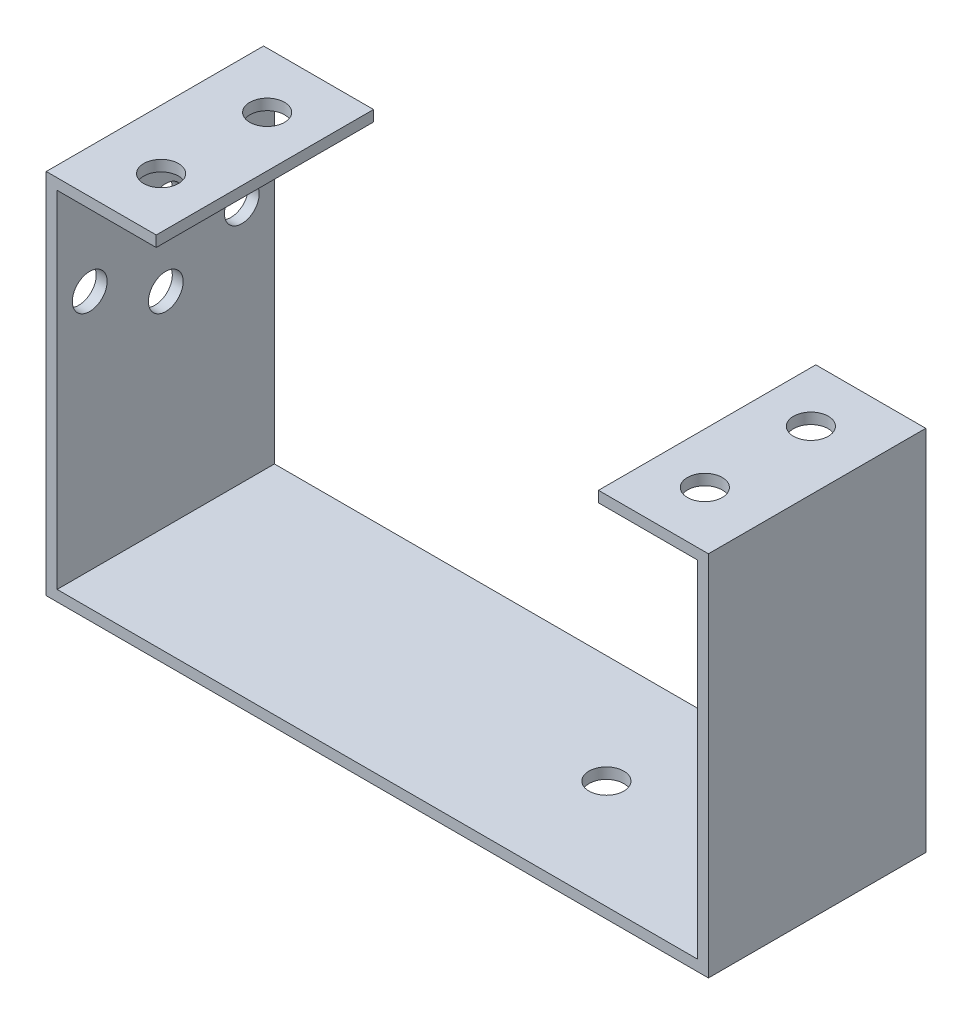
SolidWorks part; units mm, degrees
ref_plane "正面" through (0, 0, 0) normal (0, 0, 1) x (1, 0, 0)
ref_plane "平面" through (0, 0, 0) normal (0, 1, 0) x (1, 0, 0)
ref_plane "右側面" through (0, 0, 0) normal (1, 0, 0) x (0, 0, -1)
sketch "ｽｹｯﾁ2" plane through (0, 0, 0) normal (0, 1, 0) x (1, 0, 0)
  line L1 (0, 0) -> (60.94, 0)
  line L2 (0, 0) -> (0, 20)
  line L3 (0, 20) -> (60.94, 20)
  line L4 (60.94, 0) -> (60.94, 20)
extrude "ﾎﾞｽ - 押し出し1" add sketch "ｽｹｯﾁ2" along normal blind 1
sketch "ｽｹｯﾁ3" plane through (0, 1, 0) normal (0, 1, 0) x (1, 0, 0)
  line L0 (0, 0) -> (60.94, 0) construction
  line L1 (60.94, 20) -> (59.94, 20)
  line L2 (60.94, 20) -> (60.94, 0)
  line L3 (60.94, 0) -> (59.94, 0)
  line L4 (59.94, 20) -> (59.94, 0)
extrude "ﾎﾞｽ - 押し出し2" add sketch "ｽｹｯﾁ3" along normal blind 32.81
sketch "ｽｹｯﾁ4" plane through (0, 1, 0) normal (0, 1, 0) x (1, 0, 0)
  line L0 (0, 0) -> (59.94, 0) construction
  line L1 (0, 20) -> (1, 20)
  line L2 (0, 20) -> (0, 0)
  line L3 (0, 0) -> (1, 0)
  line L4 (1, 20) -> (1, 0)
extrude "ﾎﾞｽ - 押し出し3" add sketch "ｽｹｯﾁ4" along normal blind 32.81
sketch "ｽｹｯﾁ9" plane through (59.94, 0, 0) normal (-1, 0, 0) x (0, 0, 1)
  line L0 (0, 33.81) -> (0, 1) construction
  line L1 (-20, 33.81) -> (0, 33.81)
  line L2 (-20, 33.81) -> (-20, 32.81)
  line L3 (-20, 32.81) -> (0, 32.81)
  line L4 (0, 33.81) -> (0, 32.81)
extrude "ﾎﾞｽ - 押し出し8" add sketch "ｽｹｯﾁ9" along normal blind 9.12
sketch "ｽｹｯﾁ10" plane through (1, 0, 0) normal (1, 0, 0) x (0, 0, -1)
  line L0 (20, 33.81) -> (20, 1) construction
  line L1 (0, 33.81) -> (20, 33.81)
  line L2 (0, 33.81) -> (0, 32.81)
  line L3 (0, 32.81) -> (20, 32.81)
  line L4 (20, 33.81) -> (20, 32.81)
extrude "ﾎﾞｽ - 押し出し9" add sketch "ｽｹｯﾁ10" along normal blind 9.12
sketch "ｽｹｯﾁ13" plane through (0, 33.81, 0) normal (0, 1, 0) x (1, 0, 0)
  circle A0 centre (55.49, 5.12) radius 1.6
extrude "ｶｯﾄ - 押し出し2" cut sketch "ｽｹｯﾁ13" against normal blind 1
sketch "ｽｹｯﾁ14" plane through (0, 33.81, 0) normal (0, 1, 0) x (1, 0, 0)
  circle A0 centre (55.49, 14.88) radius 1.6
extrude "ｶｯﾄ - 押し出し3" cut sketch "ｽｹｯﾁ14" against normal blind 1
sketch "ｽｹｯﾁ15" plane through (0, 33.81, 0) normal (0, 1, 0) x (1, 0, 0)
  circle A0 centre (5.45, 5.12) radius 1.6
extrude "ｶｯﾄ - 押し出し4" cut sketch "ｽｹｯﾁ15" against normal blind 1
sketch "ｽｹｯﾁ16" plane through (0, 33.81, 0) normal (0, 1, 0) x (1, 0, 0)
  circle A0 centre (5.45, 14.88) radius 1.6
extrude "ｶｯﾄ - 押し出し5" cut sketch "ｽｹｯﾁ16" against normal blind 1
sketch "ｽｹｯﾁ17" plane through (0, 0, 0) normal (0, -1, 0) x (-1, 0, 0)
  circle A0 centre (-41.55, 10) radius 1.6
extrude "ｶｯﾄ - 押し出し6" cut sketch "ｽｹｯﾁ17" against normal blind 1 contours A0
sketch "ｽｹｯﾁ19" plane through (0, 0, 0) normal (-1, 0, 0) x (0, 0, 1)
  circle A0 centre (-3, 23.25) radius 1.6
extrude "ｶｯﾄ - 押し出し7" cut sketch "ｽｹｯﾁ19" against normal blind 1
sketch "ｽｹｯﾁ20" plane through (0, 0, 0) normal (-1, 0, 0) x (0, 0, 1)
  circle A0 centre (-17, 23.25) radius 1.6
extrude "ｶｯﾄ - 押し出し8" cut sketch "ｽｹｯﾁ20" against normal blind 1
sketch "ｽｹｯﾁ22" plane through (0, 0, 0) normal (-1, 0, 0) x (0, 0, 1)
  circle A0 centre (-10, 19.75) radius 1.6
extrude "ｶｯﾄ - 押し出し9" cut sketch "ｽｹｯﾁ22" against normal blind 1
sketch "ｽｹｯﾁ23" plane through (0, 0, 0) normal (-1, 0, 0) x (0, 0, 1)
  circle A0 centre (-10, 26.75) radius 1.6
extrude "ｶｯﾄ - 押し出し10" cut sketch "ｽｹｯﾁ23" against normal blind 1
